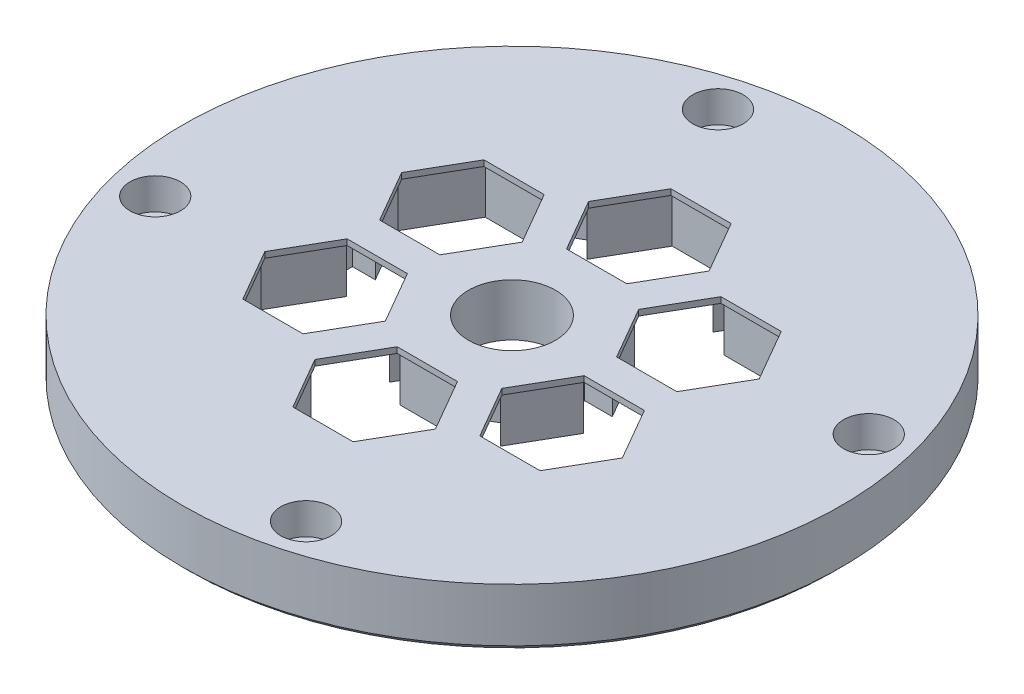
SolidWorks part; units mm, degrees
ref_plane "Front Plane" through (0, 0, 0) normal (0, 0, 1) x (1, 0, 0)
ref_plane "Top Plane" through (0, 0, 0) normal (0, 1, 0) x (1, 0, 0)
ref_plane "Right Plane" through (0, 0, 0) normal (1, 0, 0) x (0, 0, -1)
sketch "Sketch2" plane through (0, 0, 0) normal (0, 1, 0) x (1, 0, 0)
  circle A0 centre (0, 0) radius 44.5
  circle A1 centre (0, 0) radius 56.85
  dimension "D1" = 89
  dimension "D2" = 113.7
extrude "Boss-Extrude1" add sketch "Sketch2" along normal blind 1.2
sketch "Sketch3" plane through (0, 1.2, 0) normal (0, 1, 0) x (1, 0, 0)
  circle A0 centre (0, 0) radius 56.85
extrude "Boss-Extrude2" add sketch "Sketch3" along normal blind 9
sketch "Sketch4" plane through (0, 10.2, 0) normal (0, 1, 0) x (1, 0, 0)
  line L0 (0, 0) -> (0, 50.25) construction
  line L1 (-13.0057, 48.5378) -> (0, 0) construction
  circle A0 centre (0, 0) radius 50.25 construction
  circle A1 centre (-13.0057, 48.5378) radius 2.65
  circle A2 centre (48.5378, 13.0057) radius 2.65
  circle A3 centre (13.0057, -48.5378) radius 2.65
  circle A4 centre (-48.5378, -13.0057) radius 2.65
  point P14 (0, 0)
  dimension "D1" = 100.5
  dimension "D2" = 5.3
  dimension "D4" = 15
  dimension "D3" = 4
extrude "Cut-Extrude1" cut sketch "Sketch4" against normal through all
sketch "Sketch5" plane through (0, 10.2, 0) normal (0, 1, 0) x (1, 0, 0)
  circle A0 centre (0, 0) radius 7.5
  dimension "D1" = 15
extrude "Cut-Extrude2" cut sketch "Sketch5" against normal through all
sketch "Sketch6" plane through (0, 1.2, 0) normal (0, -1, 0) x (1, 0, 0)
  line L0 (0, 0) -> (0, 33.1406) construction
  line L1 (0, 0) -> (5.0107, 8.6789) construction
  line L2 (8.2583, 18.8368) -> (11.0111, 23.6047) construction
  line L3 (11.0111, 23.6047) -> (5.5055, 33.1406)
  line L4 (5.5055, 33.1406) -> (-5.5055, 33.1406)
  line L5 (-5.5055, 33.1406) -> (-11.0111, 23.6047)
  line L6 (-8.2583, 18.8368) -> (-5.5055, 14.0688) construction
  line L7 (-5.5055, 14.0688) -> (5.5055, 14.0688)
  line L8 (2.8457, 9.9289) -> (5.2359, 14.0688)
  line L9 (12.8457, 27.2494) -> (17.1758, 24.7494)
  line L10 (17.1758, 24.7494) -> (15.2064, 21.3382)
  line L11 (7.1758, 7.4289) -> (2.8457, 9.9289)
  line L12 (14.9367, 2.2665) -> (25.9478, 2.2665) construction
  line L13 (25.9478, 2.2665) -> (31.4534, 11.8024)
  line L14 (31.4534, 11.8024) -> (25.9478, 21.3382)
  line L15 (25.9478, 21.3382) -> (14.9367, 21.3382)
  line L16 (14.9367, 21.3382) -> (9.4312, 11.8024) construction
  line L17 (9.4312, 11.8024) -> (14.9367, 2.2665)
  line L18 (10.0215, -2.5) -> (10.0215, 2.5)
  line L19 (10.0215, 2.5) -> (14.8019, 2.5)
  line L20 (30.0215, 2.5) -> (30.0215, -2.5)
  line L21 (30.0215, -2.5) -> (26.0827, -2.5)
  line L22 (9.4312, -11.8024) -> (14.9367, -21.3382) construction
  line L23 (14.9367, -21.3382) -> (25.9478, -21.3382)
  line L24 (25.9478, -21.3382) -> (31.4534, -11.8024)
  line L25 (31.4534, -11.8024) -> (25.9478, -2.2665)
  line L26 (25.9478, -2.2665) -> (14.9367, -2.2665) construction
  line L27 (14.9367, -2.2665) -> (9.4312, -11.8024)
  line L28 (2.8457, -9.9289) -> (7.1758, -7.4289)
  line L29 (7.1758, -7.4289) -> (9.566, -11.5688)
  line L30 (17.1758, -24.7494) -> (12.8457, -27.2494)
  line L31 (12.8457, -27.2494) -> (10.8763, -23.8382)
  line L32 (-5.5055, -14.0688) -> (-11.0111, -23.6047) construction
  line L33 (-11.0111, -23.6047) -> (-5.5055, -33.1406)
  line L34 (-5.5055, -33.1406) -> (5.5055, -33.1406)
  line L35 (5.5055, -33.1406) -> (11.0111, -23.6047)
  line L36 (11.0111, -23.6047) -> (5.5055, -14.0688) construction
  line L37 (5.5055, -14.0688) -> (-5.5055, -14.0688)
  line L38 (-7.1758, -7.4289) -> (-2.8457, -9.9289)
  line L39 (-2.8457, -9.9289) -> (-5.2359, -14.0688)
  line L40 (-12.8457, -27.2494) -> (-17.1758, -24.7494)
  line L41 (-17.1758, -24.7494) -> (-15.2064, -21.3382)
  line L42 (-14.9367, -2.2665) -> (-25.9478, -2.2665) construction
  line L43 (-25.9478, -2.2665) -> (-31.4534, -11.8024)
  line L44 (-31.4534, -11.8024) -> (-25.9478, -21.3382)
  line L45 (-25.9478, -21.3382) -> (-14.9367, -21.3382)
  line L46 (-14.9367, -21.3382) -> (-9.4312, -11.8024) construction
  line L47 (-9.4312, -11.8024) -> (-14.9367, -2.2665)
  line L48 (-10.0215, 2.5) -> (-10.0215, -2.5)
  line L49 (-10.0215, -2.5) -> (-14.8019, -2.5)
  line L50 (-30.0215, -2.5) -> (-30.0215, 2.5)
  line L51 (-30.0215, 2.5) -> (-26.0827, 2.5)
  line L52 (-9.4312, 11.8024) -> (-14.9367, 21.3382) construction
  line L53 (-14.9367, 21.3382) -> (-25.9478, 21.3382)
  line L54 (-25.9478, 21.3382) -> (-31.4534, 11.8024)
  line L55 (-31.4534, 11.8024) -> (-25.9478, 2.2665)
  line L56 (-25.9478, 2.2665) -> (-14.9367, 2.2665) construction
  line L57 (-14.9367, 2.2665) -> (-9.4312, 11.8024)
  line L58 (-2.8457, 9.9289) -> (-7.1758, 7.4289)
  line L59 (-7.1758, 7.4289) -> (-9.566, 11.5688)
  line L60 (-17.1758, 24.7494) -> (-12.8457, 27.2494)
  line L61 (-12.8457, 27.2494) -> (-10.8763, 23.8382)
  line L62 (-9.1048, 20.77) -> (-7.0073, 17.1371) construction
  line L63 (-5.2359, 14.0688) -> (-2.8457, 9.9289)
  line L64 (-11.0111, 23.6047) -> (-8.2583, 18.8368) construction
  line L65 (-10.8763, 23.8382) -> (-9.1048, 20.77) construction
  line L66 (-9.566, 11.5688) -> (-15.2064, 21.3382) construction
  line L67 (-15.2064, 21.3382) -> (-17.1758, 24.7494)
  line L68 (-7.0073, 17.1371) -> (-5.2359, 14.0688) construction
  line L69 (5.2359, 14.0688) -> (7.0073, 17.1371) construction
  line L70 (7.0073, 17.1371) -> (9.1048, 20.77) construction
  line L71 (5.5055, 14.0688) -> (8.2583, 18.8368) construction
  line L72 (5.0107, 8.6789) -> (15.0107, 25.9994) construction
  line L73 (9.1048, 20.77) -> (10.8763, 23.8382) construction
  line L74 (10.8763, 23.8382) -> (12.8457, 27.2494)
  line L75 (15.2064, 21.3382) -> (9.566, 11.5688) construction
  line L76 (9.566, 11.5688) -> (7.1758, 7.4289)
  line L77 (14.8019, 2.5) -> (26.0827, 2.5) construction
  line L78 (26.0827, 2.5) -> (30.0215, 2.5)
  line L79 (26.0827, -2.5) -> (14.8019, -2.5) construction
  line L80 (14.8019, -2.5) -> (10.0215, -2.5)
  line L81 (9.566, -11.5688) -> (15.2064, -21.3382) construction
  line L82 (15.2064, -21.3382) -> (17.1758, -24.7494)
  line L83 (10.8763, -23.8382) -> (5.2359, -14.0688) construction
  line L84 (5.2359, -14.0688) -> (2.8457, -9.9289)
  line L85 (-5.2359, -14.0688) -> (-10.8763, -23.8382) construction
  line L86 (-10.8763, -23.8382) -> (-12.8457, -27.2494)
  line L87 (-15.2064, -21.3382) -> (-9.566, -11.5688) construction
  line L88 (-9.566, -11.5688) -> (-7.1758, -7.4289)
  line L89 (-14.8019, -2.5) -> (-26.0827, -2.5) construction
  line L90 (-26.0827, -2.5) -> (-30.0215, -2.5)
  line L91 (-26.0827, 2.5) -> (-14.8019, 2.5) construction
  line L92 (-14.8019, 2.5) -> (-10.0215, 2.5)
  arc A0 (-8.2583, 18.8368) -> (-7.0073, 17.1371) centre (0, 23.6047) ccw construction
  arc A1 (-9.1048, 20.77) -> (-8.2583, 18.8368) centre (0, 23.6047) ccw construction
  arc A2 (-8.2583, 28.3727) -> (-9.1048, 20.77) centre (0, 23.6047) ccw construction
  arc A3 (-7.0073, 17.1371) -> (0, 14.0688) centre (0, 23.6047) ccw construction
  arc A4 (8.2583, 18.8368) -> (9.1048, 20.77) centre (0, 23.6047) ccw construction
  arc A5 (0, 14.0688) -> (7.0073, 17.1371) centre (0, 23.6047) ccw construction
  arc A6 (9.1048, 20.77) -> (8.2583, 28.3727) centre (0, 23.6047) ccw construction
  arc A7 (8.2583, 28.3727) -> (-8.2583, 28.3727) centre (0, 23.6047) ccw construction
  arc A8 (7.0073, 17.1371) -> (8.2583, 18.8368) centre (0, 23.6047) ccw construction
  point P4 (0, 33.1406)
  point P20 (5.0107, 8.6789)
  point P71 (0, 0)
  dimension "D2" = 19.0718
  dimension "D1" = 33.1406
  dimension "D3" = 30.0215
  dimension "D4" = 30
  dimension "D5" = 5
  dimension "D6" = 20
  dimension "D7" = 6
extrude "Cut-Extrude4" cut sketch "Sketch6" against normal through all contours L90 L43 L44 L45 L41 L40 L86 L33 L34 L35 L31 L30 L82 L23 L24 L25 L21 L20 L78 L13 L14 L15 L10 L9 L74 L3 L4 L5 L61 L60 L67 region at (12.6524, 1.2, 25.0869)
sketch "Sketch7" plane through (0, 10.2, 0) normal (0, 1, 0) x (1, 0, 0)
  line L0 (-17.1758, 24.7494) -> (-7.1758, 7.4289)
  line L1 (-7.1758, 7.4289) -> (-2.8457, 9.9289)
  line L2 (-2.8457, 9.9289) -> (-12.8457, 27.2494)
  line L3 (-12.8457, 27.2494) -> (-17.1758, 24.7494)
  line L4 (17.1758, 24.7494) -> (12.8457, 27.2494)
  line L5 (12.8457, 27.2494) -> (2.8457, 9.9289)
  line L6 (2.8457, 9.9289) -> (7.1758, 7.4289)
  line L7 (7.1758, 7.4289) -> (17.1758, 24.7494)
  line L8 (30.0215, -2.5) -> (30.0215, 2.5)
  line L9 (30.0215, 2.5) -> (10.0215, 2.5)
  line L10 (10.0215, 2.5) -> (10.0215, -2.5)
  line L11 (10.0215, -2.5) -> (30.0215, -2.5)
  line L12 (12.8457, -27.2494) -> (17.1758, -24.7494)
  line L13 (17.1758, -24.7494) -> (7.1758, -7.4289)
  line L14 (7.1758, -7.4289) -> (2.8457, -9.9289)
  line L15 (2.8457, -9.9289) -> (12.8457, -27.2494)
  line L16 (-17.1758, -24.7494) -> (-12.8457, -27.2494)
  line L17 (-12.8457, -27.2494) -> (-2.8457, -9.9289)
  line L18 (-2.8457, -9.9289) -> (-7.1758, -7.4289)
  line L19 (-7.1758, -7.4289) -> (-17.1758, -24.7494)
  line L20 (-30.0215, 2.5) -> (-30.0215, -2.5)
  line L21 (-30.0215, -2.5) -> (-10.0215, -2.5)
  line L22 (-10.0215, -2.5) -> (-10.0215, 2.5)
  line L23 (-10.0215, 2.5) -> (-30.0215, 2.5)
  point P31 (0, 0)
  dimension "D1" = 6
extrude "Boss-Extrude3" add sketch "Sketch7" against normal blind 1
sketch "Sketch8" plane through (0, 10.2, 0) normal (0, 1, 0) x (1, 0, 0)
  line L0 (0, 0) -> (0, -23.6047) construction
  line L9 (5.5426, -14.0047) -> (-5.5426, -14.0047)
  line L10 (-5.5426, -14.0047) -> (-11.0851, -23.6047)
  line L11 (-11.0851, -23.6047) -> (-5.5426, -33.2047)
  line L12 (-5.5426, -33.2047) -> (5.5426, -33.2047)
  line L13 (5.5426, -33.2047) -> (11.0851, -23.6047)
  line L14 (11.0851, -23.6047) -> (5.5426, -14.0047)
  line L15 (5.1962, -14.6047) -> (-5.1962, -14.6047)
  line L16 (-5.1962, -14.6047) -> (-10.3923, -23.6047)
  line L17 (-10.3923, -23.6047) -> (-5.1962, -32.6047)
  line L18 (-5.1962, -32.6047) -> (5.1962, -32.6047)
  line L19 (5.1962, -32.6047) -> (10.3923, -23.6047)
  line L20 (10.3923, -23.6047) -> (5.1962, -14.6047)
  circle A0 centre (0, -23.6047) radius 9.6 construction
  circle A1 centre (0, -23.6047) radius 9 construction
  point P63 (0, 0)
  dimension "D2" = 19.2
  dimension "D3" = 18
  dimension "D1" = 23.6047
extrude "Boss-Extrude4" add sketch "Sketch8" against normal blind 1
pattern_circular "CirPattern1" count 6 over 360 about axis through (0, 0, 0) along (0, 1, 0) of "Boss-Extrude4" reverse direction yes
sketch "Sketch9" plane through (0, 10.2, 0) normal (0, 1, 0) x (1, 0, 0)
  circle A0 centre (-13.0057, 48.5378) radius 4.35
  circle A1 centre (48.5378, 13.0057) radius 4.35
  circle A2 centre (13.0057, -48.5378) radius 4.35
  circle A3 centre (-48.5378, -13.0057) radius 4.35
  point P3 (0, 0)
  point P12 (0, 0)
  dimension "D1" = 8.7
  dimension "D2" = 4
extrude "Cut-Extrude5" cut sketch "Sketch9" against normal blind 5.4
chamfer "Chamfer1" distance 1 angle 45 2 edges at (0, 0, 44.5) (0, 0, 56.85)
